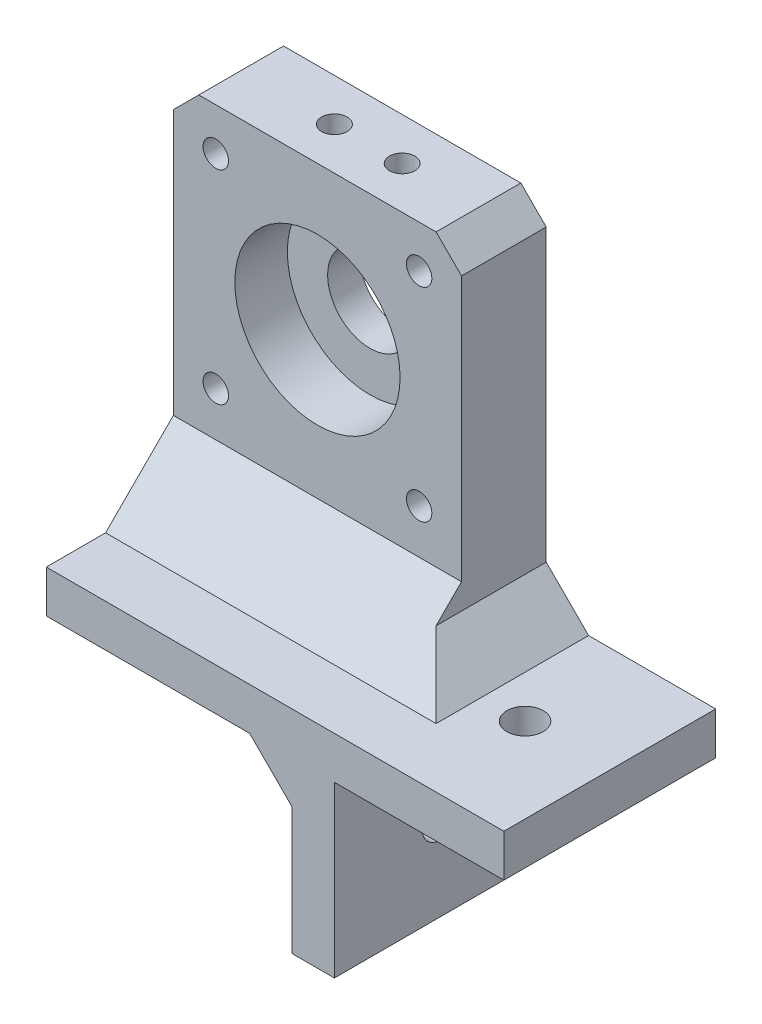
SolidWorks part; units mm, degrees
ref_plane "前视基准面" through (0, 0, 0) normal (0, 0, 1) x (1, 0, 0)
ref_plane "上视基准面" through (0, 0, 0) normal (0, 1, 0) x (1, 0, 0)
ref_plane "右视基准面" through (0, 0, 0) normal (1, 0, 0) x (0, 0, -1)
sketch "草图1" plane through (0, 0, 0) normal (0, 0, 1) x (1, 0, 0)
  line L0 (0, 0) -> (0, 20)
  line L1 (0, 20) -> (20, 20)
  line L2 (20, 20) -> (20, 25)
  line L3 (20, 25) -> (0, 25)
  line L4 (0, 25) -> (0, 67.25)
  line L5 (0, 67.25) -> (-34, 67.25)
  line L6 (-34, 67.25) -> (-34, 20)
  line L7 (-34, 20) -> (-5, 20)
  line L8 (-5, 20) -> (-5, 0)
  line L9 (-5, 0) -> (0, 0)
  circle A0 centre (-17, 50.25) radius 5
  circle A1 centre (-29, 62.25) radius 1.5
  circle A2 centre (-5, 62.25) radius 1.5
  circle A3 centre (-29, 38.25) radius 1.5
  circle A4 centre (-5, 38.25) radius 1.5
  dimension "D3" = 10
  dimension "D13" = 3
  dimension "D1" = 20
  dimension "D2" = 20
  dimension "D4" = 12
  dimension "D5" = 12
  dimension "D6" = 12
  dimension "D7" = 12
  dimension "D8" = 12
  dimension "D9" = 5
  dimension "D10" = 5
  dimension "D11" = 30.25
  dimension "D12" = 12
  dimension "D14" = 5
  dimension "D15" = 5
  dimension "D16" = 5
extrude "凸台-拉伸1" add sketch "草图1" along normal blind 25
sketch "草图2" plane through (0, 0, 0) normal (1, 0, 0) x (0, 0, -1)
  line L0 (-25, 0) -> (0, 0) construction
  circle A0 centre (-12.5, 10) radius 2.15
  point P4 (-12.5, 0)
  dimension "D2" = 4.3
  dimension "D1" = 10
extrude "切除-拉伸1" cut sketch "草图2" against normal blind 30
sketch "草图3" plane through (0, 20, 0) normal (0, -1, 0) x (1, 0, 0)
  line L0 (20, 25) -> (20, 0) construction
  circle A0 centre (10, 12.5) radius 2.15
  point P4 (20, 12.5)
  dimension "D2" = 4.3
  dimension "D1" = 10
extrude "切除-拉伸2" cut sketch "草图3" against normal blind 30
sketch "草图4" plane through (0, 0, 0) normal (0, 0, -1) x (-1, 0, 0)
  line L0 (34, 67.25) -> (34, 20) construction
  line L1 (0, 67.25) -> (34, 67.25)
  line L2 (0, 67.25) -> (0, 25)
  line L3 (0, 25) -> (34, 25)
  line L4 (34, 67.25) -> (34, 25)
  line L6 (-20, 25) -> (0, 25) construction
extrude "切除-拉伸3" cut sketch "草图4" against normal blind 15
chamfer "倒角1" distance 5 angle 45 2 edges at (-5, 20, 12.5) (0, 25, 20)
chamfer "倒角2" distance 3 angle 45 2 edges at (-34, 67.25, 20) (0, 67.25, 20)
sketch "草图6" plane through (0, 0, 15) normal (0, 0, -1) x (-1, 0, 0)
  circle A0 centre (17, 50.25) radius 9.75
  dimension "D1" = 19.5
extrude "切除-拉伸5" cut sketch "草图6" against normal blind 6.2
sketch "草图7" plane through (0, 0, 25) normal (0, 0, 1) x (1, 0, 0)
  line L0 (-34, 20) -> (-10, 20)
  line L1 (-10, 20) -> (-5, 15)
  line L2 (-5, 15) -> (-5, 0)
  line L3 (-5, 0) -> (-34, 20)
extrude "凸台-拉伸2" add sketch "草图7" against normal blind 5
mirror "镜向1" about plane through (0, 0, 25) normal (0, 0, 1) of bodies 112
sketch "草图8" plane through (0, 0, 0) normal (0, 0, -1) x (-1, 0, 0)
  line L1 (-29.2783, 78.0994) -> (62.2837, 78.0994)
  line L2 (-29.2783, 78.0994) -> (-29.2783, -7.8499)
  line L3 (-29.2783, -7.8499) -> (62.2837, -7.8499)
  line L4 (62.2837, 78.0994) -> (62.2837, -7.8499)
extrude "切除-拉伸6" cut sketch "草图8" against normal up to vertex (25 mm away) up to point (-34, 64.25, 25)
chamfer "倒角3" distance 8 angle 45 1 edges at (-14.5, 25, 35)
sketch "草图9" plane through (-34, 0, 0) normal (-1, 0, 0) x (0, 0, 1)
  line L0 (25, 64.25) -> (25, 20) construction
  line L1 (50, 20) -> (30, 20) construction
  circle A0 centre (40, 24) radius 1.5
  circle A1 centre (32, 24) radius 1.5
  point P8 (0, 0)
  dimension "D4" = 3
  dimension "D1" = 8
  dimension "D2" = 7
  dimension "D3" = 4
extrude "切除-拉伸7" cut sketch "草图9" against normal blind 10
sketch "草图10" plane through (0, 67.25, 0) normal (0, 1, 0) x (1, 0, 0)
  line L1 (-3, -25) -> (-31, -25) construction
  line L2 (-3, -25) -> (-3, -35) construction
  circle A0 centre (-12, -30) radius 1.5
  circle A1 centre (-20, -30) radius 1.5
  point P8 (0, 0)
  dimension "D4" = 3
  dimension "D1" = 9
  dimension "D2" = 8
  dimension "D3" = 5
extrude "切除-拉伸8" cut sketch "草图10" against normal blind 5
